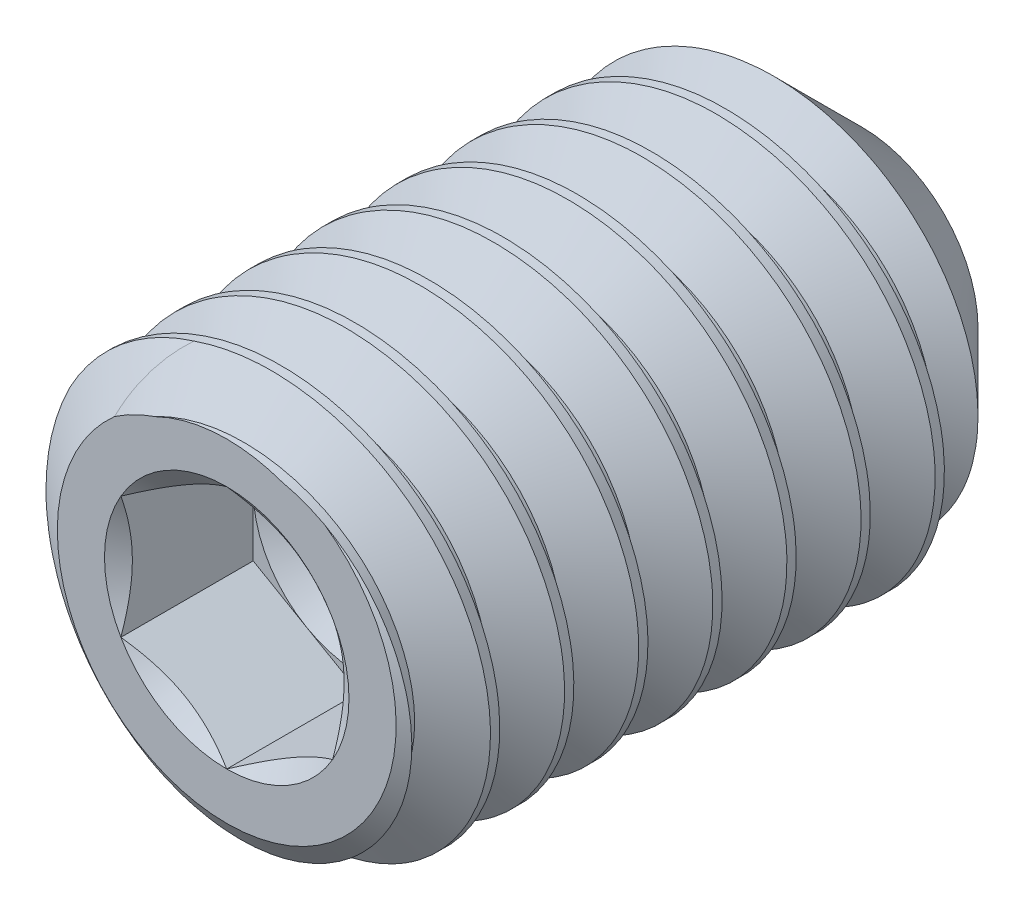
SolidWorks part; units mm, degrees
ref_plane "Front" through (0, 0, 0) normal (0, 0, 1) x (1, 0, 0)
ref_plane "Top" through (0, 0, 0) normal (0, 1, 0) x (1, 0, 0)
ref_plane "Right" through (0, 0, 0) normal (1, 0, 0) x (0, 0, -1)
sketch "Body Sketch" plane through (0, 0, 0) normal (1, 0, 0) x (0, 0, -1)
  line L0 (-2.6707, 0) -> (-2.6707, 1.6)
  line L1 (-2.6707, 1.6) -> (-2.3907, 2)
  line L2 (-2.3907, 2) -> (2.4252, 2)
  line L3 (2.4252, 2) -> (3.3293, 1.0959)
  line L4 (0.0173, 2) -> (0.0173, -2) construction
  line L5 (2.6707, 0) -> (-2.6707, 0)
  line L6 (-2.6707, 1.6) -> (-2.6707, -1.6) construction
  line L7 (2.6707, 0) -> (3.3293, 1.0959)
  line L8 (2.6707, 0) -> (3.3293, -1.0959) construction
  line L10 (2.6707, 0) -> (3.3293, 0) construction
  line L11 (3.3293, 1.0959) -> (3.3293, 0) construction
  point P11 (0.0173, 0)
  dimension "Length" = 6
  dimension "Top Chamfer" = 35
  dimension "Diameter" = 4
  dimension "D1" = 3.2
  dimension "D2" = 118
  dimension "D3" = 45
revolve "Body Revolve" add sketch "Body Sketch" angle 360 about L5
ref_plane "Bottom of Tip Plane" through (0, 0, -3.3293) normal (0, 0, 1) x (1, 0, 0)
sketch "Spiral Sketch" plane through (0, 0, -3.3293) normal (0, 0, 1) x (1, 0, 0)
  circle A0 centre (0, 0) radius 2 construction
  circle A1 centre (0, 0) radius 2
curve "Helix/Spiral" pitch 0.7 height 6.7 radius 2 centre (0, 0, -3.3293) axis (0, 0, 1) start towards (0, 1, 0) parameters "Thread Pitch"=0.7
sketch "Cut Sweep Sketch" plane through (0, 0, 0) normal (1, 0, 0) x (0, 0, -1)
  line L0 (3.3293, 2) -> (3.9418, 2)
  line L1 (3.9418, 2) -> (3.6793, 1.5453)
  line L2 (3.6793, 1.5453) -> (3.5918, 1.5453)
  line L3 (3.5918, 1.5453) -> (3.3293, 2)
  line L4 (3.4605, 1.7727) -> (3.8105, 1.7727) construction
  line L6 (-2.3907, 2) -> (2.4252, 2) construction
  dimension "D1" = 0.0875
  dimension "D3" = 60
  dimension "D2" = 0.35
sweep "Cut Sweep" cut profiles "Cut Sweep Sketch" path "Helix/Spiral" align with end faces yes
sketch "Hex Sketch" plane through (0, 0, 2.6707) normal (0, 0, 1) x (1, 0, 0)
  line L1 (0, 1.1547) -> (-1, 0.5774)
  line L2 (-1, 0.5774) -> (-1, -0.5774)
  line L3 (-1, -0.5774) -> (0, -1.1547)
  line L4 (0, -1.1547) -> (1, -0.5774)
  line L5 (1, -0.5774) -> (1, 0.5774)
  line L6 (1, 0.5774) -> (0, 1.1547)
  circle A0 centre (0, 0) radius 1 construction
  dimension "Hex" = 2
extrude "Hex Extrude" cut sketch "Hex Sketch" against normal blind 1.25
sketch "Hex Entry Sketch" plane through (0, 0, 2.6707) normal (0, 0, 1) x (1, 0, 0)
  circle A0 centre (0, 0) radius 1.1547
extrude "Hex Entry Extrude" cut sketch "Hex Entry Sketch" against normal through all draft 55
sketch "Hex Bottom Sketch" plane through (0, 0, 1.4207) normal (0, 0, 1) x (1, 0, 0)
  circle A0 centre (0, 0) radius 1 construction
  circle A1 centre (0, 0) radius 1
extrude "Hex Bottom Extrude" cut sketch "Hex Bottom Sketch" against normal through all draft 60
equation "\"D1@Cut Sweep Sketch\" = \"Thread Pitch@Helix/Spiral\" * .125"
equation "\"D2@Cut Sweep Sketch\" = \"Thread Pitch@Helix/Spiral\" * .5"
equation "\"D3@Helix/Spiral\" = \"Length@Body Sketch\" + \"Thread Pitch@Helix/Spiral\""
equation "\"hex Depth@Hex Extrude\" = \"Hex@Hex Sketch\" * .625"
equation "\"D1@Body Sketch\" = \"Diameter@Body Sketch\" * .8"
equation "\"Diameter\"= 4mm"
equation "\"Thread Pitch\"= 0.7mm"
equation "\"Hex Size\"= 2.0mm"
equation "\"Diameter@Body Sketch\"=\"Diameter\""
equation "\"Thread Pitch@Helix/Spiral\"=\"Thread Pitch\""
equation "\"Hex@Hex Sketch\"=\"Hex Size\""
